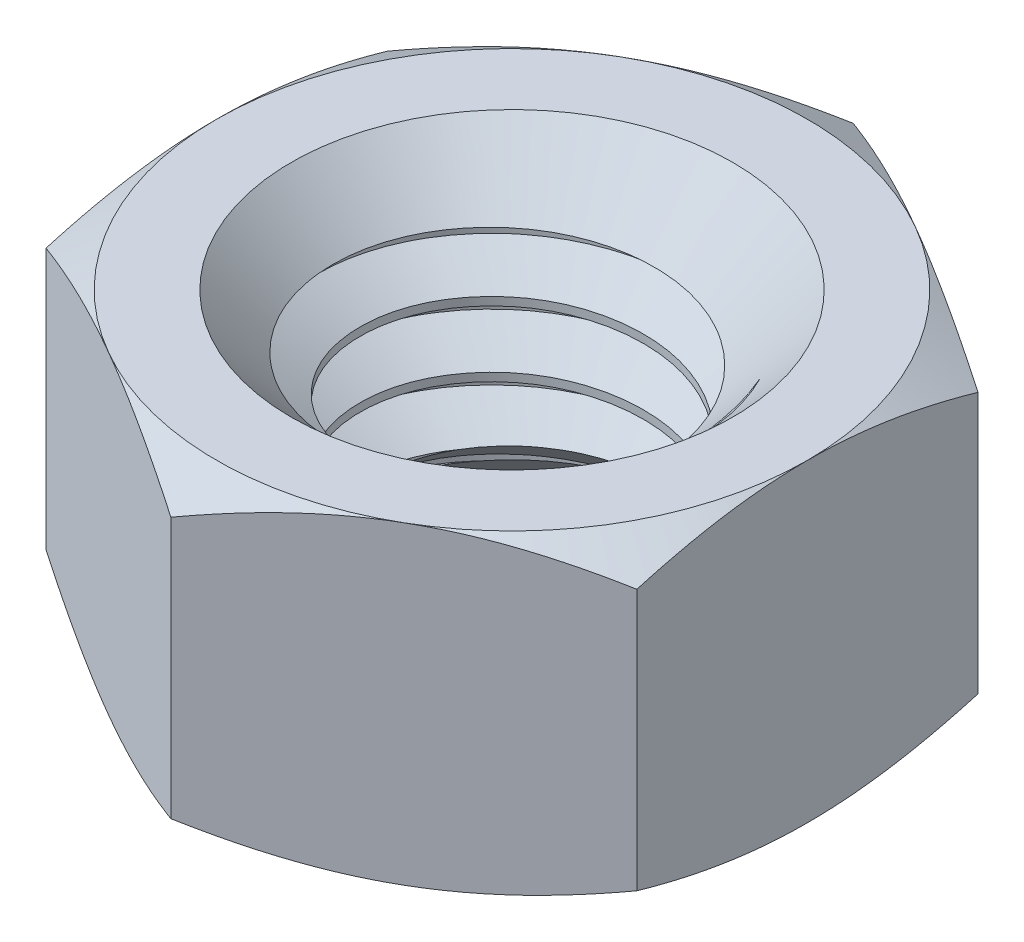
SolidWorks part; units mm, degrees
ref_plane "Front Plane" through (0, 0, 0) normal (0, 0, 1) x (1, 0, 0)
ref_plane "Top Plane" through (0, 0, 0) normal (0, 1, 0) x (1, 0, 0)
ref_plane "Right Plane" through (0, 0, 0) normal (1, 0, 0) x (0, 0, -1)
sketch "Sketch1" plane through (0, 0, 0) normal (0, 1, 0) x (1, 0, 0)
  line L1 (6.35, 3.6662) -> (0, 7.3323) construction
  line L2 (0, 7.3323) -> (-6.35, 3.6662) construction
  line L3 (-6.35, 3.6662) -> (-6.35, -3.6662) construction
  line L4 (-6.35, -3.6662) -> (0, -7.3323) construction
  line L5 (0, -7.3323) -> (6.35, -3.6662) construction
  line L6 (6.35, -3.6662) -> (6.35, 3.6662) construction
  line L7 (0, -2.5576) -> (0, -3.9688) construction
  circle A0 centre (0, 0) radius 6.35 construction
  circle A1 centre (0, 0) radius 3.9688 construction
  point P10 (0, -3.9688)
  dimension "Thread Size" = 7.9375
  dimension "Width" = 12.7
  dimension "Thread Pitch" = 1.4111
sketch "Sketch9" plane through (0, 0, 0) normal (0, 0, 1) x (1, 0, 0)
  line L0 (0, 3.3734) -> (0, -3.3734) construction
  dimension "Height" = 6.7469
sketch "Sketch2" plane through (0, 0, 0) normal (0, 1, 0) x (1, 0, 0)
  line L0 (-6.35, -3.6662) -> (0, -7.3323) construction
  line L1 (0, -7.3323) -> (6.35, -3.6662) construction
  line L2 (6.35, -3.6662) -> (6.35, 3.6662) construction
  line L3 (6.35, 3.6662) -> (0, 7.3323) construction
  line L4 (0, 7.3323) -> (-6.35, 3.6662) construction
  line L5 (-6.35, 3.6662) -> (-6.35, -3.6662) construction
  line L6 (-6.35, -3.6662) -> (0, -7.3323)
  line L7 (0, -7.3323) -> (6.35, -3.6662)
  line L8 (6.35, -3.6662) -> (6.35, 3.6662)
  line L9 (6.35, 3.6662) -> (0, 7.3323)
  line L10 (0, 7.3323) -> (-6.35, 3.6662)
  line L11 (-6.35, 3.6662) -> (-6.35, -3.6662)
  circle A0 centre (0, 0) radius 3.9688 construction
  circle A1 centre (0, 0) radius 3.9688
extrude "Boss-Extrude1" add sketch "Sketch2" along normal mid plane 6.7469
sketch "Sketch3" plane through (0, 3.3734, 0) normal (0, 1, 0) x (1, 0, 0)
  circle A3 centre (0, 0) radius 6.35
  dimension "D1" = 12.7
extrude "Cut-Extrude1" cut sketch "Sketch3" against normal through all draft 60 flip side to cut
mirror "Mirror1" about plane through (0, 0, 0) normal (0, 1, 0) of "Cut-Extrude1"
chamfer "Chamfer1" distance 0.7761 angle 45 2 edges at (0, -3.3734, 3.9688) (0, 3.3734, 3.9688)
sketch "Sketch4" plane through (0, 3.3734, 0) normal (0, 1, 0) x (1, 0, 0)
  circle A2 centre (0, 0) radius 3.9688 construction
  circle A3 centre (0, 0) radius 3.9688
curve "Helix/Spiral1" pitch 1.4111 height 8.158 radius 3.9688 centre (0, 3.3734, 0) axis (0, -1, 0) start towards (0, 0, 1)
sketch "Sketch5" plane through (0, 0, 0) normal (0, 0, 1) x (1, 0, 0)
  line L4 (-4.1215, 3.2852) -> (-2.8994, 3.9908) construction
  line L5 (-2.8994, 3.9908) -> (-4.1215, 4.6964) construction
  line L6 (-4.1215, 4.6964) -> (-4.1215, 3.2852) construction
  line L7 (-3.9688, 3.3734) -> (-3.9688, 4.6082) construction
  line L8 (-4.1215, 3.9908) -> (-3.9688, 3.9908) construction
  line L9 (-3.9688, 3.9908) -> (-3.0522, 3.9908) construction
  line L10 (-3.0522, 3.9908) -> (-2.8994, 3.9908) construction
  line L11 (-3.0522, 3.9026) -> (-3.0522, 4.079)
  line L12 (-4.0451, 3.3293) -> (-4.0451, 4.6523)
  line L13 (-3.0522, 4.079) -> (-4.0451, 4.6523)
  line L14 (-3.0522, 3.9026) -> (-4.0451, 3.3293)
  point P13 (-4.0451, 3.9908)
  dimension "D1" = 1.4111
  dimension "D2" = 0.1764
sweep "Sweep1" add profiles "Sketch5" path "Helix/Spiral1"
sketch "Sketch6" plane through (0, 3.3734, 0) normal (0, 1, 0) x (1, 0, 0)
  circle A0 centre (0, 0) radius 4.7449 construction
  circle A3 centre (0, 0) radius 4.7449
extrude "Cut-Extrude2" cut sketch "Sketch6" along normal through all and the other way blind 10 draft 45
sketch "Sketch10" plane through (0, -3.3734, 0) normal (0, -1, 0) x (1, 0, 0)
  circle A1 centre (0, 0) radius 4.7449
  circle A2 centre (0, 0) radius 4.7449
  dimension "D1" = 0
extrude "Cut-Extrude3" cut sketch "Sketch10" against normal through all draft 45 and the other way through all
equation "\"D1@Boss-Extrude1\" = \"Height@Sketch9\""
equation "\"D3@Helix/Spiral1\"= \"Height@Sketch9\" + \"Thread Pitch@Sketch1\""
equation "\"D4@Helix/Spiral1\" = \"Thread Pitch@Sketch1\""
equation "\"D2@Sketch5\"=\"D1@Sketch5\"/8"
equation "\"D1@Sketch5\"=\"Thread Pitch@Sketch1\""
equation "\"D1@Chamfer1\"=\"Thread Pitch@Sketch1\"*0.55"
equation "\"D1@Sketch3\"=\"Width@Sketch1\""
